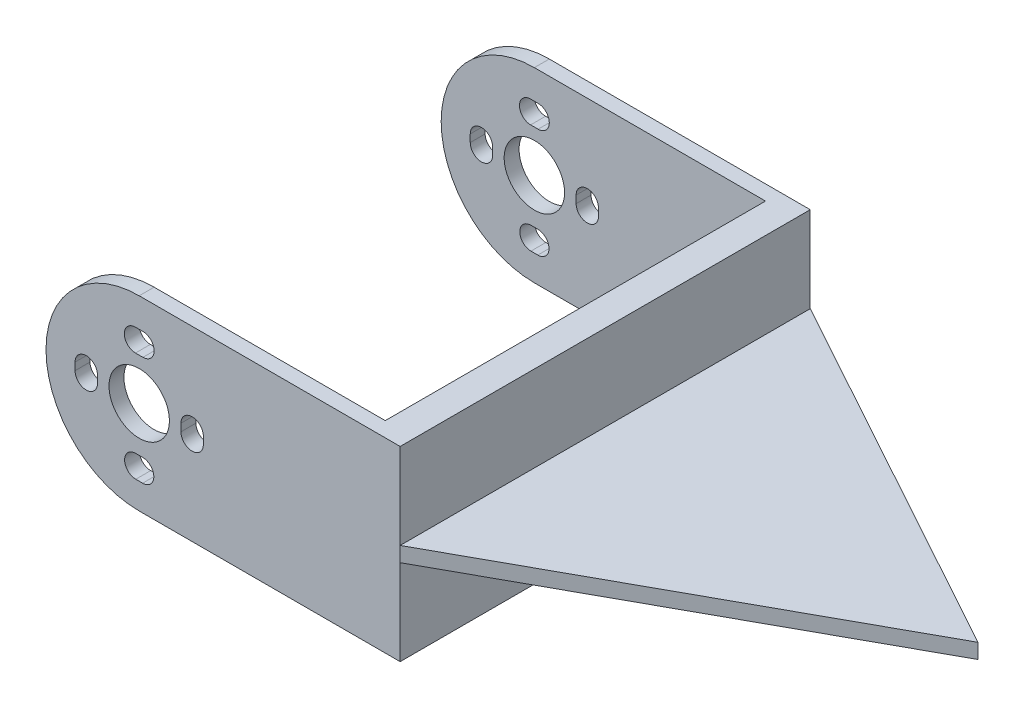
SolidWorks part; units mm, degrees
ref_plane "前基準面" through (0, 0, 0) normal (0, 0, 1) x (1, 0, 0)
ref_plane "上基準面" through (0, 0, 0) normal (0, 1, 0) x (1, 0, 0)
ref_plane "右基準面" through (0, 0, 0) normal (1, 0, 0) x (0, 0, -1)
sketch "Sketch1" plane through (0, 0, 0) normal (0, 0, 1) x (1, 0, 0)
  line L0 (-29.0958, -4.1361) -> (32.9042, -4.1361) construction
  line L1 (-18.5958, 6.3639) -> (22.4042, 6.3639)
  line L2 (-18.5958, 6.3639) -> (-18.5958, -14.6361)
  line L3 (-18.5958, -14.6361) -> (22.4042, -14.6361)
  line L4 (22.4042, 6.3639) -> (22.4042, -14.6361)
  line L5 (-29.0958, 16.8639) -> (32.9042, 16.8639)
  line L6 (-29.0958, 16.8639) -> (-29.0958, -25.1361)
  line L7 (-29.0958, -25.1361) -> (32.9042, -25.1361)
  line L8 (32.9042, 16.8639) -> (32.9042, -25.1361)
  line L9 (1.9042, 16.8639) -> (1.9042, -25.1361) construction
  line L10 (22.4042, -4.1361) -> (-18.5958, -4.1361) construction
  line L11 (1.9042, 6.3639) -> (1.9042, -14.6361) construction
  point P16 (1.9042, -4.1361)
  point P17 (1.9042, -4.1361)
  dimension "D1" = 21
  dimension "D2" = 41
  dimension "D3" = 62
  dimension "D4" = 42
extrude "Boss-Extrude1" add sketch "Sketch1" along normal blind 42
sketch "Sketch2" plane through (0, 0, 42) normal (0, 0, 1) x (1, 0, 0)
  line L0 (-18.5958, -4.1361) -> (-29.0958, -4.1361) construction
  line L1 (-25.0958, -4.1361) -> (-29.0958, -4.1361) construction
  line L3 (-29.0958, 16.8639) -> (-29.0958, -25.1361) construction
  line L4 (-18.5958, 6.3639) -> (-18.5958, -14.6361) construction
  line L5 (-29.0958, 8.3639) -> (-25.0958, 8.3639)
  line L6 (-29.0958, 8.3639) -> (-29.0958, -16.6361)
  line L7 (-29.0958, -16.6361) -> (-25.0958, -16.6361)
  line L8 (-25.0958, 8.3639) -> (-25.0958, -16.6361)
  dimension "D1" = 25
  dimension "D2" = 4
extrude "Boss-Extrude2" add sketch "Sketch2" along normal blind 4.5
extrude "Boss-Extrude3" add sketch "Sketch2<2>" against normal blind 45.55
sketch "Sketch2<2>" plane through (0, 0, 42) normal (0, 0, 1) x (1, 0, 0) same geometry as "Sketch2"
sketch "Sketch3" plane through (0, 0, 46.5) normal (0, 0, 1) x (1, 0, 0)
  line L0 (-60.5958, 2.9639) -> (-59.5958, 2.9639) construction
  line L1 (-25.0958, 8.3639) -> (-60.0958, 8.3639)
  line L2 (-25.0958, 8.3639) -> (-25.0958, -16.6361)
  line L3 (-25.0958, -16.6361) -> (-60.0958, -16.6361)
  line L4 (-60.0958, 8.3639) -> (-60.0958, -16.6361)
  line L5 (-60.5958, 4.4639) -> (-59.5958, 4.4639)
  line L6 (-60.5958, 1.4639) -> (-59.5958, 1.4639)
  line L7 (-60.0958, 8.3639) -> (-60.0958, -16.6361) construction
  line L8 (-60.5559, -11.6762) -> (-59.6357, -11.6762) construction
  line L9 (-60.5559, -10.1762) -> (-59.6357, -10.1762)
  line L10 (-60.5559, -13.1762) -> (-59.6357, -13.1762)
  line L11 (-60.0958, -4.1361) -> (-72.5958, -4.1361) construction
  line L12 (-67.1958, -3.6361) -> (-67.1958, -4.6361) construction
  line L15 (-65.6958, -3.6361) -> (-65.6958, -4.6361)
  line L16 (-68.6958, -3.6361) -> (-68.6958, -4.6361)
  line L17 (-52.9958, -3.6361) -> (-52.9958, -4.6361) construction
  line L18 (-51.4958, -3.6361) -> (-51.4958, -4.6361)
  line L19 (-54.4958, -3.6361) -> (-54.4958, -4.6361)
  line L20 (-60.0958, -4.1361) -> (-25.0958, -4.1361) construction
  arc A0 (-60.0958, 8.3639) -> (-60.0958, -16.6361) centre (-60.0958, -4.1361) ccw
  circle A1 centre (-60.0958, -4.1361) radius 4.05
  arc A3 (-60.5958, 4.4639) -> (-60.5958, 1.4639) centre (-60.5958, 2.9639) ccw
  arc A4 (-59.5958, 1.4639) -> (-59.5958, 4.4639) centre (-59.5958, 2.9639) ccw
  arc A5 (-60.5559, -10.1762) -> (-60.5559, -13.1762) centre (-60.5559, -11.6762) ccw
  arc A6 (-59.6357, -13.1762) -> (-59.6357, -10.1762) centre (-59.6357, -11.6762) ccw
  arc A9 (-65.6958, -3.6361) -> (-68.6958, -3.6361) centre (-67.1958, -3.6361) ccw
  arc A10 (-68.6958, -4.6361) -> (-65.6958, -4.6361) centre (-67.1958, -4.6361) ccw
  arc A11 (-51.4958, -3.6361) -> (-54.4958, -3.6361) centre (-52.9958, -3.6361) ccw
  arc A12 (-54.4958, -4.6361) -> (-51.4958, -4.6361) centre (-52.9958, -4.6361) ccw
  point P9 (-60.0958, 2.9639)
  point P14 (-58.0958, 2.9639)
  point P15 (-62.0958, 2.9639)
  point P19 (-60.0958, -11.6762)
  point P25 (-67.1958, -4.1361)
  point P31 (-67.1958, -2.1361)
  point P32 (-67.1958, -6.1361)
  point P34 (-65.6958, -4.1361)
  point P37 (-52.9958, -4.1361)
  point P42 (-52.9958, -2.1361)
  point P43 (-52.9958, -6.1361)
  line M15 (-29.0958, 8.3639) -> (-29.0958, -16.6361)
  line M16 (-29.0958, -16.6361) -> (-25.0958, -16.6361)
  line M17 (-25.0958, -16.6361) -> (-25.0958, 8.3639)
  line M18 (-25.0958, 8.3639) -> (-29.0958, 8.3639)
  dimension "D2" = 4
  dimension "D10" = 5.6
  dimension "D9" = 4
  dimension "D1" = 35
  dimension "D3" = 3
  dimension "D4" = 5.6
  dimension "D5" = 25
  dimension "D6" = 6.0402
  dimension "D7" = 0
  dimension "D8" = 3
  dimension "D11" = 5.6
  dimension "D12" = 3
  dimension "D13" = 4
extrude "Boss-Extrude6" add sketch "Sketch3" along normal blind 2 contours A5 L9 L4 A1 L6 A3 L5 A0 L10 A10 L16 A9 L15 | A6 L10 L4 L3 L1 L5 A4 L6 A1 L9 A12 L19 A11 L18 M15 | M18 M15 M16 M17 region at (-27.0958, -4.1361, 46.5) region at (-43.7932, -4.1343, 46.5) region at (-60.3753, 6.4139, 46.5)
extrude "Boss-Extrude7" add sketch "Sketch3<8>" against normal blind 53 contours A5 L9 L4 A1 L6 A3 L5 A0 L10 A10 L16 A9 L15 | A6 L10 L4 L3 L1 L5 A4 L6 A1 L9 A12 L19 A11 L18 M15 | M18 M15 M16 M17 region at (-27.0958, -4.1361, 46.5) region at (-43.7932, -4.1343, 46.5) region at (-60.3753, 6.4139, 46.5)
sketch "Sketch3<8>" plane through (0, 0, 46.5) normal (0, 0, 1) x (1, 0, 0) same geometry as "Sketch3"
extrude "Cut-Extrude1" cut sketch "Sketch3<11>" against normal blind 51 contours A6 L10 L4 L3 L1 L5 A4 L6 A1 L9 A12 L19 A11 L18 M15 | A5 L9 L4 A1 L6 A3 L5 A0 L10 A10 L16 A9 L15 region at (-43.7932, -4.1343, 46.5) region at (-60.3753, 6.4139, 46.5)
sketch "Sketch3<11>" plane through (0, 0, 46.5) normal (0, 0, 1) x (1, 0, 0) same geometry as "Sketch3"
sketch "草圖1" plane through (0, 16.8639, 0) normal (0, 1, 0) x (1, 0, 0)
  line L1 (12.7042, -35.25) -> (4.2042, -35.25)
  line L2 (12.7042, -35.25) -> (12.7042, -29.75)
  line L3 (12.7042, -29.75) -> (4.2042, -29.75)
  line L4 (4.2042, -35.25) -> (4.2042, -29.75)
  line L5 (32.9042, -42) -> (-29.0958, -42) construction
  line L7 (22.4042, -42) -> (22.4042, 0) construction
  dimension "D1" = 8.5
  dimension "D2" = 5.5
  dimension "D3" = 9.7
  dimension "D4" = 6.75
extrude "除料-伸長1" cut sketch "草圖1" against normal blind 40
sketch "草圖3" plane through (0, 0, 0) normal (0, 0, -1) x (-1, 0, 0)
  line L0 (29.0958, 8.3639) -> (29.0958, 16.8639)
  line L1 (29.0958, 16.8639) -> (-32.9042, 16.8639)
  line L2 (-32.9042, 16.8639) -> (-32.9042, -25.1361)
  line L3 (-32.9042, -25.1361) -> (29.0958, -25.1361)
  line L5 (29.0958, -25.1361) -> (29.0958, -16.6361)
  line L6 (29.0958, -16.6361) -> (25.0958, -16.6361)
  line L7 (25.0958, -16.6361) -> (25.0958, 8.3639)
  line L8 (25.0958, 8.3639) -> (29.0958, 8.3639)
extrude "除料-伸長3" cut sketch "草圖3" against normal blind 42
sketch "草圖5" plane through (0, 8.3639, 0) normal (0, 1, 0) x (1, 0, 0)
  line L0 (-25.0958, 6.5) -> (-25.0958, -48.5)
  line L1 (-25.0958, -21) -> (24.9042, -21) construction
  line L2 (-25.0958, 6.5) -> (24.9042, -21)
  line L3 (24.9042, -21) -> (-25.0958, -48.5)
extrude "填料-伸長1" add sketch "草圖5" against normal blind 13.5
extrude "除料-伸長4" cut sketch "草圖5<2>" against normal blind 11.5
sketch "草圖5<2>" plane through (0, 8.3639, 0) normal (0, 1, 0) x (1, 0, 0) same geometry as "草圖5"
